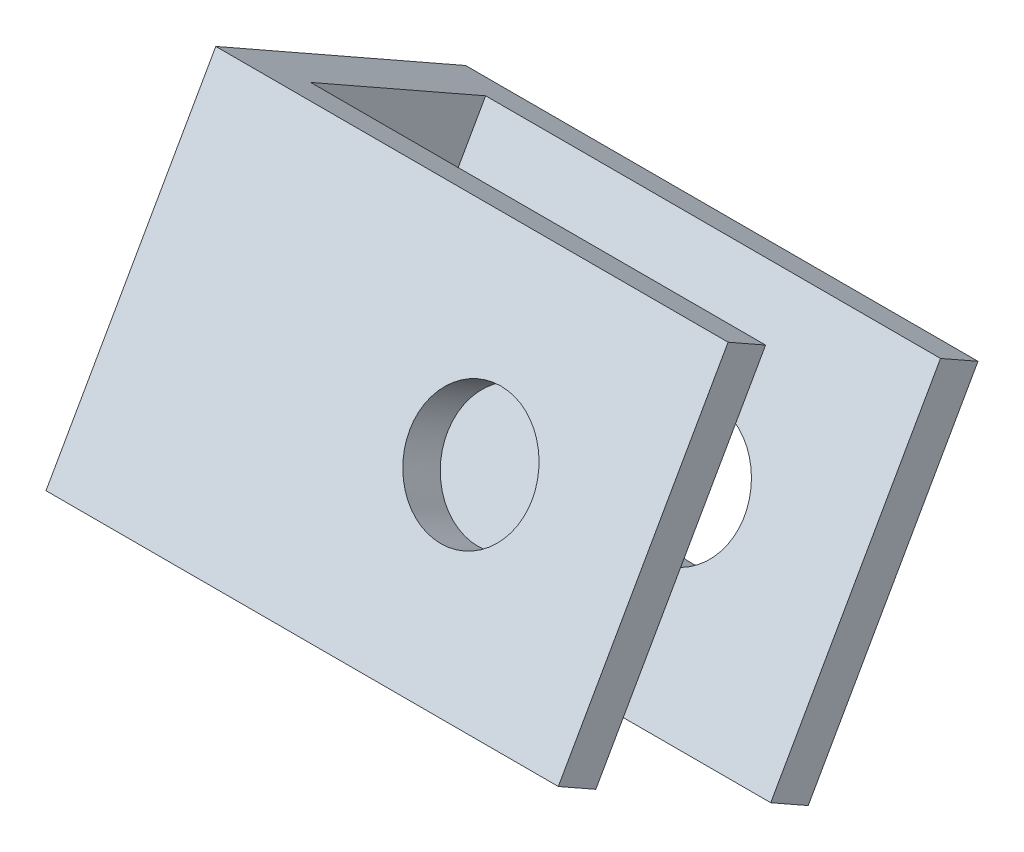
SolidWorks part; units mm, degrees
ref_plane "Front Plane" through (0, 0, 0) normal (0, 0, 1) x (1, 0, 0)
ref_plane "Top Plane" through (0, 0, 0) normal (0, 1, 0) x (1, 0, 0)
ref_plane "Right Plane" through (0, 0, 0) normal (1, 0, 0) x (0, 0, -1)
ref_plane "Plane1" through (0, -217.9452, -384.9482) normal (0, -0.4927, -0.8702) x (-1, 0, 0)
sketch "Sketch1" plane through (0, -217.9452, -384.9482) normal (0, -0.4927, -0.8702) x (-1, 0, 0)
  line L0 (487.45, 1279.1709) -> (468.654, 1279.1709) construction
  line L1 (487.45, 1279.1709) -> (468.654, 1279.1709) construction
  line L2 (487.45, 1288.6959) -> (487.45, 1269.6459)
  line L3 (487.45, 1427.6969) -> (487.45, 1247.6609) construction
  line L4 (487.45, 1288.6959) -> (459.129, 1288.6959)
  line L5 (459.129, 1288.6959) -> (459.129, 1269.6459)
  line L6 (459.129, 1269.6459) -> (487.45, 1269.6459)
  circle A0 centre (468.654, 1279.1709) radius 3.3782
  point P6 (487.45, 1279.1709)
  dimension "D1" = 6.7564
  dimension "D2" = 9.525
  dimension "D3" = 9.525
extrude "Boss-Extrude1" add sketch "Sketch1" along normal mid plane 15.875
sketch "Sketch2" plane through (0, 1104.8565, -625.534) normal (0, -0.8702, 0.4927) x (1, 0, 0)
  line L0 (-487.45, -442.3632) -> (-459.129, -442.3632) construction
  line L1 (-484.275, -436.807) -> (-452.4806, -436.807)
  line L2 (-484.275, -436.807) -> (-484.275, -447.9195)
  line L3 (-484.275, -447.9195) -> (-452.4806, -447.9195)
  line L4 (-452.4806, -436.807) -> (-452.4806, -447.9195)
  line L8 (-459.129, -434.4257) -> (-487.45, -434.4257)
  line L9 (-487.45, -434.4257) -> (-487.45, -450.3007)
  line L10 (-487.45, -450.3007) -> (-459.129, -450.3007)
  line L11 (-459.129, -450.3007) -> (-459.129, -434.4257)
  line L12 (-459.129, -434.4257) -> (-487.45, -434.4257) construction
  line L13 (-487.45, -434.4257) -> (-487.45, -450.3007) construction
  line L14 (-487.45, -450.3007) -> (-459.129, -450.3007) construction
  line L15 (-459.129, -450.3007) -> (-459.129, -434.4257) construction
  dimension "D1" = 11.1125
  dimension "D3" = 3.175
  dimension "D2" = 0
extrude "Cut-Extrude1" cut sketch "Sketch2" against normal through all
sketch "Sketch3" plane through (-487.45, 0, 0) normal (-1, 0, 0) x (0, 0, 1)
  line L0 (-1019.8678, 903.4887) -> (-1010.4822, 886.9113) construction
  line L1 (-1022.0823, 891.2893) -> (-1008.2677, 899.1107) construction
  line L4 (-1003.5749, 890.8219) -> (-1012.9605, 907.3994)
  line L5 (-1012.9605, 907.3994) -> (-1026.7751, 899.5781)
  line L6 (-1026.7751, 899.5781) -> (-1017.3895, 883.0006)
  line L7 (-1017.3895, 883.0006) -> (-1003.5749, 890.8219)
  line L8 (-1003.5749, 890.8219) -> (-1012.9605, 907.3994) construction
  line L9 (-1012.9605, 907.3994) -> (-1026.7751, 899.5781) construction
  line L10 (-1026.7751, 899.5781) -> (-1017.3895, 883.0006) construction
  line L11 (-1017.3895, 883.0006) -> (-1003.5749, 890.8219) construction
  circle A0 centre (-1015.175, 895.2) radius 2.5527
  point P10 (0, 0)
  dimension "D2" = 5.1054
  dimension "D1" = 0
extrude "Cut-Extrude2" cut sketch "Sketch3" against normal through all
